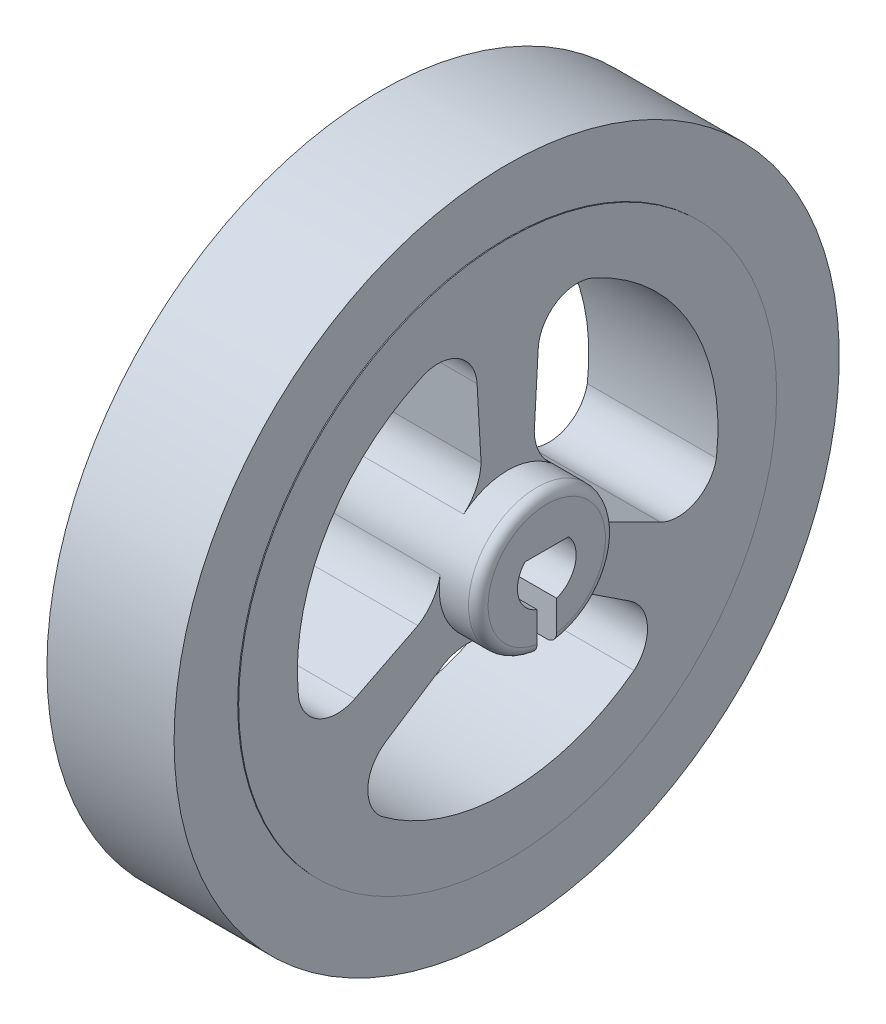
SolidWorks part; units mm, degrees
material "Borracha de silicone"
ref_plane "Plano frontal" through (0, 0, 0) normal (0, 0, 1) x (1, 0, 0)
ref_plane "Plano superior" through (0, 0, 0) normal (0, 1, 0) x (1, 0, 0)
ref_plane "Plano direito" through (0, 0, 0) normal (1, 0, 0) x (0, 0, -1)
sketch "Esboço1" plane through (0, 0, 0) normal (1, 0, 0) x (0, 0, -1)
  line L0 (1.118, 1) -> (-1.118, 1)
  line L1 (-0.5, -1.4142) -> (-0.5, -3.4641)
  line L2 (0.5, -1.4142) -> (0.5, -3.4641)
  line L3 (0, -1.5) -> (-1.0555, -1.5) construction
  line L4 (3.2296, -3.4333) -> (6.2449, -5.4106)
  line L5 (-1.3585, 4.5136) -> (-1.5633, 8.1136)
  line L6 (1.3585, 4.5136) -> (1.5633, 8.1136)
  line L7 (2.25, 2.681) -> (-2.25, 2.681) construction
  line L8 (4.5881, -1.0803) -> (7.8082, -2.703)
  line L9 (-4.5881, -1.0803) -> (-7.8082, -2.703)
  line L10 (-3.2296, -3.4333) -> (-6.2449, -5.4106)
  arc A0 (0.5, -3.4641) -> (-0.5, -3.4641) centre (0, 0) ccw
  circle A1 centre (0, 0) radius 13.75
  arc A2 (-1.118, 1) -> (-0.5, -1.4142) centre (0, 0) ccw
  arc A3 (0.5, -1.4142) -> (1.118, 1) centre (0, 0) ccw
  arc A4 (-4.5313, 9.7483) -> (-10.7079, -0.9499) centre (0, 0) ccw
  arc A5 (-1.5633, 8.1136) -> (-4.5313, 9.7483) centre (-3.56, 8) ccw
  arc A6 (1.5633, 8.1136) -> (4.5313, 9.7483) centre (3.56, 8) cw
  arc A7 (-2.25, 2.681) -> (-1.3585, 4.5136) centre (-3.8571, 4.5959) ccw
  arc A8 (2.25, 2.681) -> (1.3585, 4.5136) centre (3.8571, 4.5959) cw
  arc A9 (3.4468, 0.6081) -> (4.5881, -1.0803) centre (5.9088, 1.0424) ccw
  arc A10 (1.1968, -3.289) -> (3.2296, -3.4333) centre (2.0516, -5.6383) cw
  arc A11 (7.8082, -2.703) -> (10.671, -1.3011) centre (8.7082, -0.9169) ccw
  arc A12 (6.2449, -5.4106) -> (6.4623, -8.5908) centre (5.1482, -7.0831) cw
  arc A13 (-1.1968, -3.289) -> (-3.2296, -3.4333) centre (-2.0516, -5.6383) ccw
  arc A14 (-3.4468, 0.6081) -> (-4.5881, -1.0803) centre (-5.9088, 1.0424) cw
  arc A15 (-6.2449, -5.4106) -> (-6.4623, -8.5908) centre (-5.1482, -7.0831) ccw
  arc A16 (-7.8082, -2.703) -> (-10.7079, -0.9499) centre (-8.7082, -0.9169) cw
  arc A17 (-6.4623, -8.5908) -> (6.4623, -8.5908) centre (0, 0) ccw
  arc A18 (10.671, -1.3011) -> (4.5313, 9.7483) centre (0, 0) ccw
  point P50 (0, 0)
  dimension "D1" = 7
  dimension "D2" = 27.5
  dimension "D3" = 3
  dimension "D6" = 21.5
  dimension "D11" = 2.5
  dimension "D8" = 2
  dimension "D9" = 8
  dimension "D4" = 0.5
  dimension "D5" = 2.5
  dimension "D7" = 3.6
  dimension "D10" = 4.5
  dimension "D12" = 1.1
  dimension "D13" = 3
extrude "Ressalto-extrusão1" add sketch "Esboço1" along normal blind 5.3 and the other way blind 3.3 contours A3 L2 A0 L1 A2 L0 region at (0, 1.0987, 0)
extrude "Ressalto-extrusão2" add sketch "Esboço1<3>" along normal mid plane 6.6 contours A1 A18 A11 L8 A9 A0 A10 L4 A12 A17 A15 L10 A13 A14 L9 A16 A4 A5 L5 A7 A8 L6 A6 region at (0, 0, 13.3611)
sketch "Esboço1<3>" plane through (0, 0, 0) normal (1, 0, 0) x (0, 0, -1) same geometry as "Esboço1"
fillet "Filete2" radius 0.5 3 edges at (-3.3, -3.3945, 0.8529) (-3.3, -3.3945, -0.8529) (5.3, 3.5, 0)
sketch "Esboço2" plane through (0, 0, 0) normal (1, 0, 0) x (0, 0, -1)
  circle A0 centre (0, 0) radius 13.75
  circle A1 centre (0, 0) radius 17
  dimension "D1" = 34
  dimension "D2" = 27.5
extrude "Ressalto-extrusão3" add sketch "Esboço2" along normal mid plane 6.5
ref_plane "基准面1" through (0, 0, 0) normal (1, 0, 0) x (0, 0, -1)
ref_axis "基准轴1" through (-3.3, 0, 0) along (1, 0, 0)
ref_point "点1"
